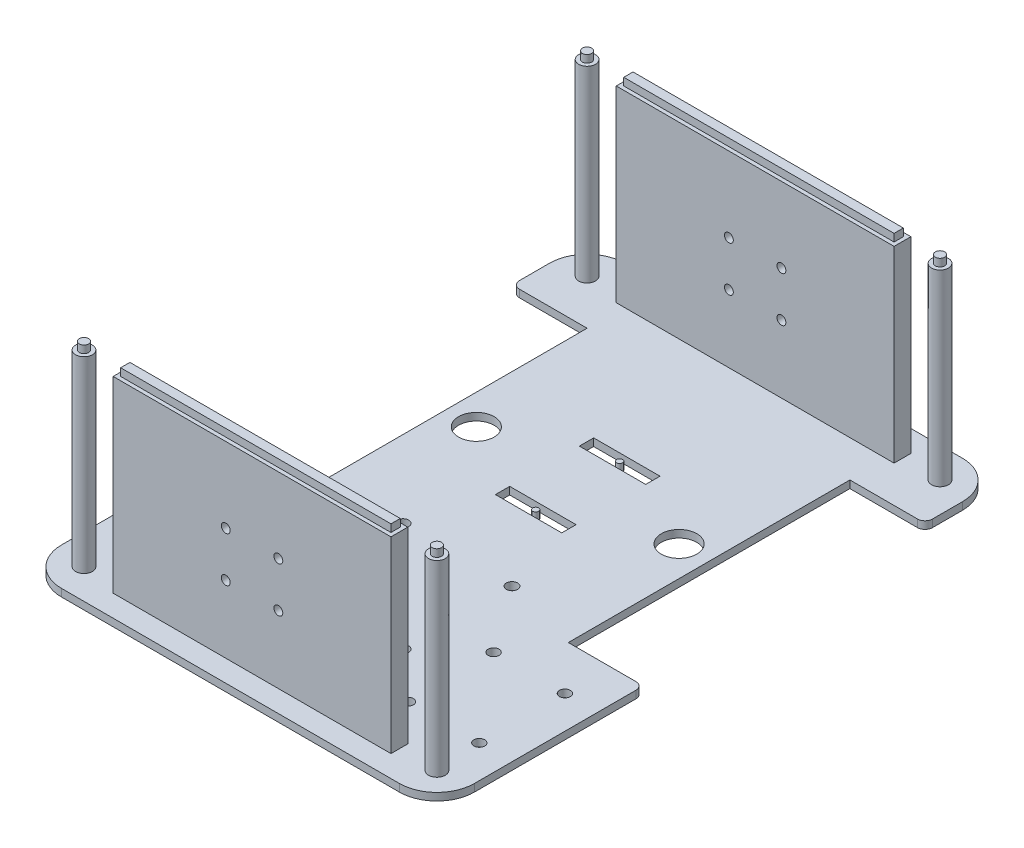
SolidWorks part; units mm, degrees
material "ABS"
ref_plane "Front Plane" through (0, 0, 0) normal (0, 0, 1) x (1, 0, 0)
ref_plane "Top Plane" through (0, 0, 0) normal (0, 1, 0) x (1, 0, 0)
ref_plane "Right Plane" through (0, 0, 0) normal (1, 0, 0) x (0, 0, -1)
sketch "Sketch2" plane through (0, 0, 0) normal (0, 1, 0) x (1, 0, 0)
  line L0 (-148.7583, 0) -> (98.0966, 0) construction
  line L1 (-69.85, -95.25) -> (69.85, -95.25)
  line L2 (-69.85, -95.25) -> (-69.85, 95.25)
  line L3 (-69.85, 95.25) -> (69.85, 95.25)
  line L4 (69.85, -95.25) -> (69.85, 95.25)
  line L5 (-69.85, -95.25) -> (69.85, 95.25) construction
  line L6 (-69.85, 95.25) -> (69.85, -95.25) construction
  line L7 (0, 121.1686) -> (0, -125.6862) construction
  point P0 (0, 0)
  dimension "D1" = 190.5
  dimension "D2" = 139.7
extrude "Base Plate" add sketch "Sketch2" along normal blind 2.54
sketch "Sketch4" plane through (0, 2.54, 0) normal (0, 1, 0) x (1, 0, 0)
  line L0 (0, -95.25) -> (0, 95.25) construction
  line L1 (-69.85, -95.25) -> (69.85, -95.25) construction
  line L2 (69.85, 95.25) -> (-69.85, 95.25) construction
  line L3 (-34.66, -69.85) -> (-34.66, -40.894) construction
  line L4 (-34.66, -40.894) -> (-58.79, -40.894) construction
  line L5 (-58.79, -40.894) -> (-58.79, -69.85) construction
  line L6 (-58.79, -69.85) -> (-34.66, -69.85) construction
  line L7 (69.85, -95.25) -> (69.85, 95.25) construction
  line L8 (-69.85, 95.25) -> (-69.85, -95.25) construction
  circle A0 centre (-58.79, -69.85) radius 1.8415
  circle A1 centre (-34.66, -69.85) radius 1.8415
  circle A2 centre (-34.66, -40.894) radius 1.8415
  circle A3 centre (-58.79, -40.894) radius 1.8415
  circle A4 centre (34.66, -69.85) radius 1.8415
  circle A5 centre (58.79, -69.85) radius 1.8415
  circle A6 centre (58.79, -40.894) radius 1.8415
  circle A7 centre (34.66, -40.894) radius 1.8415
  point P0 (-58.79, -69.85)
  point P1 (-58.79, -40.894)
  point P2 (-34.66, -40.894)
  point P3 (-34.66, -69.85)
  dimension "D4" = 3.683
  dimension "D1" = 28.956
  dimension "D2" = 24.13
  dimension "D3" = 11.06
  dimension "D5" = 25.4
extrude "L-Bracket holes" cut sketch "Sketch4" against normal blind 6.35
sketch "Sketch5" plane through (0, 2.54, 0) normal (0, 1, 0) x (1, 0, 0)
  line L0 (-69.85, -25.4) -> (-44.45, -25.4)
  line L1 (-69.85, 95.25) -> (-69.85, -95.25) construction
  line L2 (-44.45, -25.4) -> (-44.45, 69.85)
  line L3 (-44.45, 69.85) -> (-69.85, 69.85)
  line L4 (-69.85, 69.85) -> (-69.85, -25.4)
  line L5 (-69.85, -95.25) -> (69.85, -95.25) construction
  line L6 (69.85, 95.25) -> (-69.85, 95.25) construction
  line L7 (0, -95.25) -> (0, 95.25) construction
  line L8 (-58.79, -40.894) -> (-34.66, -40.894) construction
  line L9 (44.45, 69.85) -> (69.85, 69.85)
  line L10 (44.45, -25.4) -> (44.45, 69.85)
  line L11 (69.85, -25.4) -> (44.45, -25.4)
  line L12 (69.85, 69.85) -> (69.85, -25.4)
  dimension "D1" = 25.4
  dimension "D2" = 95.25
  dimension "D3" = 25.4
extrude "Steering Wheels Holes" cut sketch "Sketch5" against normal blind 6.35
fillet "Fillet1" radius 12.7 4 edges at (69.85, 1.27, -95.25) (-69.85, 1.27, -95.25) (69.85, 1.27, 95.25) (-69.85, 1.27, 95.25)
fillet "Fillet2" radius 2.54 4 edges at (69.85, 1.27, -69.85) (69.85, 1.27, 25.4) (-69.85, 1.27, 25.4) (-69.85, 1.27, -69.85)
sketch "Sketch6" plane through (0, 2.54, 0) normal (0, 1, 0) x (1, 0, 0)
  line L0 (-69.85, -95.25) -> (-69.85, 95.25) construction
  line L1 (-69.85, -95.25) -> (69.85, -95.25) construction
  line L2 (0, -88.935) -> (0, 95.5267) construction
  line L3 (-69.85, -27.94) -> (69.85, -27.94) construction
  point P0 (-59.69, -85.09)
  point P12 (-59.69, 29.21)
  point P13 (59.69, -85.09)
  point P14 (59.69, 29.21)
  dimension "D1" = 10.16
  dimension "D2" = 10.16
sketch "Sketch13" plane through (0, 2.54, 0) normal (0, 1, 0) x (1, 0, 0)
  line L0 (-69.85, -55.245) -> (69.85, -55.245) construction
  line L2 (-69.85, -27.94) -> (-69.85, -82.55) construction
  line L3 (69.85, -82.55) -> (69.85, -27.94) construction
  line L5 (-34.66, -69.85) -> (-34.66, -40.894) construction
  line L6 (34.66, -69.85) -> (34.66, -40.894) construction
  line L7 (-18.415, -55.245) -> (18.415, -55.245) construction
  line L8 (18.415, -55.245) -> (18.415, -18.415) construction
  line L9 (18.415, -18.415) -> (-18.415, -18.415) construction
  line L10 (-18.415, -18.415) -> (-18.415, -55.245) construction
  circle A0 centre (-18.415, -18.415) radius 1.905
  circle A1 centre (-18.415, -55.245) radius 1.905
  circle A2 centre (18.415, -55.245) radius 1.905
  circle A3 centre (18.415, -18.415) radius 1.905
  dimension "D1" = 3.81
  dimension "D4" = 36.83
  dimension "D5" = 36.83
extrude "Holes for L298" cut sketch "Sketch13" against normal blind 6.35
sketch "Sketch14" plane through (0, 2.54, 0) normal (0, 1, 0) x (1, 0, 0)
  line L0 (11.2203, 34.01) -> (-11.2203, 34.01)
  line L1 (11.2203, 5.61) -> (-11.2203, 5.61)
  line L2 (11.2203, 5.61) -> (11.2203, 10.44)
  line L3 (11.2203, 10.44) -> (-11.2203, 10.44)
  line L4 (0, 95.25) -> (0, -56.8347) construction
  line L5 (57.15, 95.25) -> (-57.15, 95.25) construction
  line L6 (-11.2203, 5.61) -> (-11.2203, 10.44)
  line L7 (-44.45, 22.225) -> (44.45, 22.225) construction
  line L8 (-44.45, -25.4) -> (-44.45, 69.85) construction
  line L9 (44.45, 69.85) -> (44.45, -25.4) construction
  line L10 (11.2203, 5.61) -> (-11.2203, 10.44) construction
  line L11 (11.2203, 10.44) -> (-11.2203, 5.61) construction
  line L12 (-11.2203, 38.84) -> (-11.2203, 34.01)
  line L13 (11.2203, 38.84) -> (-11.2203, 38.84)
  line L14 (11.2203, 38.84) -> (11.2203, 34.01)
  circle A2 centre (0, 8.025) radius 0.9906
  circle A3 centre (0, 36.425) radius 0.9906
  dimension "D3" = 4.83
  dimension "D2" = 1.9812
  dimension "D1" = 14.2
extrude "Cut-Extrude4" cut sketch "Sketch14" against normal blind 6.35
sketch "Sketch15" plane through (0, 2.54, 0) normal (0, 1, 0) x (1, 0, 0)
  line L0 (-69.85, -95.25) -> (-69.85, 95.25) construction
  line L1 (-69.85, 95.25) -> (69.85, 95.25) construction
  line L2 (0, 95.25) -> (0, 49.0943) construction
  line L3 (0, 121.1686) -> (0, -125.6862) construction
  circle A0 centre (-59.69, 85.09) radius 1.57
  circle A1 centre (-59.69, 85.09) radius 2.84
  point P0 (-59.69, 85.09)
  point P5 (59.69, 85.09)
  dimension "D3" = 3.14
  dimension "D1" = 10.16
  dimension "D2" = 10.16
  dimension "D4" = 1.27
sketch "Sketch18" plane through (0, 2.54, 0) normal (0, 1, 0) x (1, 0, 0)
  line L0 (-44.45, 22.225) -> (44.45, 22.225) construction
  line L1 (-44.45, -25.4) -> (-44.45, 69.85) construction
  line L2 (44.45, 69.85) -> (44.45, -25.4) construction
  line L3 (0, 95.25) -> (0, -95.25) construction
  line L4 (57.15, 95.25) -> (-57.15, 95.25) construction
  line L5 (-57.15, -95.25) -> (57.15, -95.25) construction
  circle A0 centre (34.29, 22.225) radius 6
  circle A1 centre (-34.29, 22.225) radius 6
  point P12 (-34.29, 22.225)
  point P13 (34.29, 22.225)
  dimension "D2" = 12
  dimension "D1" = 10.16
extrude "Boss-Extrude3" add sketch "Sketch15" along normal blind 63.5
extrude "Boss-Extrude4" add sketch "Sketch15<2>" along normal blind 66.04 contours A0 region at (-59.69, 2.54, -85.09)
sketch "Sketch15<2>" plane through (0, 2.54, 0) normal (0, 1, 0) x (1, 0, 0) same geometry as "Sketch15"
mirror "Mirror1" about plane through (0, 0, 0) normal (1, 0, 0) of "Boss-Extrude4"
mirror "Mirror2" about plane through (0, 0, 0) normal (1, 0, 0) of "Boss-Extrude3"
sketch "Sketch23" plane through (0, 2.54, 0) normal (0, 1, 0) x (1, 0, 0)
  line L0 (0, 95.25) -> (0, -95.25) construction
  line L1 (-69.85, -27.94) -> (-69.85, -82.55) construction
  line L2 (-57.15, -95.25) -> (57.15, -95.25) construction
  circle A0 centre (-59.69, -85.09) radius 1.57
  circle A1 centre (-59.69, -85.09) radius 2.84
  dimension "D1" = 3.14
  dimension "D3" = 10.16
  dimension "D4" = 10.16
  dimension "D2" = 1.27
extrude "Boss-Extrude5" add sketch "Sketch23" along normal blind 63.5
extrude "Boss-Extrude6" add sketch "Sketch23<2>" along normal blind 66.04 contours A0 region at (-59.69, 2.54, 85.09)
sketch "Sketch23<2>" plane through (0, 2.54, 0) normal (0, 1, 0) x (1, 0, 0) same geometry as "Sketch23"
mirror "Mirror3" about plane through (0, 0, 0) normal (1, 0, 0) of "Boss-Extrude6", "Boss-Extrude5"
sketch "Sketch24" plane through (0, 2.54, 0) normal (0, 1, 0) x (1, 0, 0)
  line L0 (-59.69, -87.93) -> (59.69, -87.93) construction
  line L1 (-59.69, -82.25) -> (59.69, -82.25) construction
  line L2 (-59.69, 82.25) -> (59.69, 82.25) construction
  line L3 (-46.99, -87.93) -> (46.99, -87.93)
  line L4 (-46.99, -87.93) -> (-46.99, -82.25)
  line L5 (-46.99, -82.25) -> (46.99, -82.25)
  line L6 (46.99, -87.93) -> (46.99, -82.25)
  line L7 (59.69, 87.93) -> (-59.69, 87.93) construction
  line L9 (-46.99, 82.25) -> (46.99, 82.25)
  line L10 (-46.99, 82.25) -> (-46.99, 87.93)
  line L11 (-46.99, 87.93) -> (46.99, 87.93)
  line L12 (46.99, 82.25) -> (46.99, 87.93)
  circle A0 centre (-59.69, -85.09) radius 2.84 construction
  circle A1 centre (59.69, -85.09) radius 2.84 construction
  circle A2 centre (-59.69, -85.09) radius 2.84 construction
  circle A3 centre (-59.69, 85.09) radius 2.84 construction
  circle A4 centre (-59.69, 85.09) radius 2.84 construction
  circle A5 centre (59.69, 85.09) radius 2.84 construction
  circle A6 centre (59.69, 85.09) radius 2.84 construction
  dimension "D1" = 12.7
  dimension "D2" = 12.7
  dimension "D3" = 12.7
  dimension "D4" = 12.7
extrude "Boss-Extrude7" add sketch "Sketch24" along normal blind 63.5
sketch "Sketch25" plane through (0, 66.04, 0) normal (0, 1, 0) x (1, 0, 0)
  line L8 (-45.72, -83.52) -> (-45.72, -86.66)
  line L9 (-45.72, -86.66) -> (45.72, -86.66)
  line L10 (45.72, -86.66) -> (45.72, -83.52)
  line L11 (45.72, -83.52) -> (-45.72, -83.52)
  line L12 (-45.72, -83.52) -> (-45.72, -86.66)
  line L13 (-45.72, -86.66) -> (45.72, -86.66)
  line L14 (45.72, -86.66) -> (45.72, -83.52)
  line L15 (45.72, -83.52) -> (-45.72, -83.52)
  line L20 (-45.72, 86.66) -> (-45.72, 83.52)
  line L21 (-45.72, 83.52) -> (45.72, 83.52)
  line L22 (45.72, 83.52) -> (45.72, 86.66)
  line L23 (45.72, 86.66) -> (-45.72, 86.66)
  line L24 (-45.72, 86.66) -> (-45.72, 83.52)
  line L25 (-45.72, 83.52) -> (45.72, 83.52)
  line L26 (45.72, 83.52) -> (45.72, 86.66)
  line L27 (45.72, 86.66) -> (-45.72, 86.66)
  dimension "D1" = 1.27
  dimension "D2" = 1.27
extrude "Boss-Extrude8" add sketch "Sketch25" along normal blind 2.54
sketch "Sketch26" plane through (0, 0, -87.93) normal (0, 0, -1) x (-1, 0, 0)
  line L0 (0, 66.04) -> (0, 83.3576) construction
  line L1 (-46.99, 66.04) -> (46.99, 66.04) construction
  line L2 (-8.89, 40.64) -> (-8.89, -18.1923) construction
  circle A0 centre (-8.89, 40.64) radius 1.5
  circle A1 centre (-8.89, 25.4) radius 1.5
  circle A2 centre (8.89, 25.4) radius 1.5
  circle A3 centre (8.89, 40.64) radius 1.5
  dimension "D1" = 3
  dimension "D3" = 3
  dimension "D2" = 8.89
  dimension "D4" = 15.24
  dimension "D5" = 25.4
extrude "Cut-Extrude5" cut sketch "Sketch26" against normal through all
extrude "Cut-Extrude6" cut sketch "Sketch18" against normal through all
